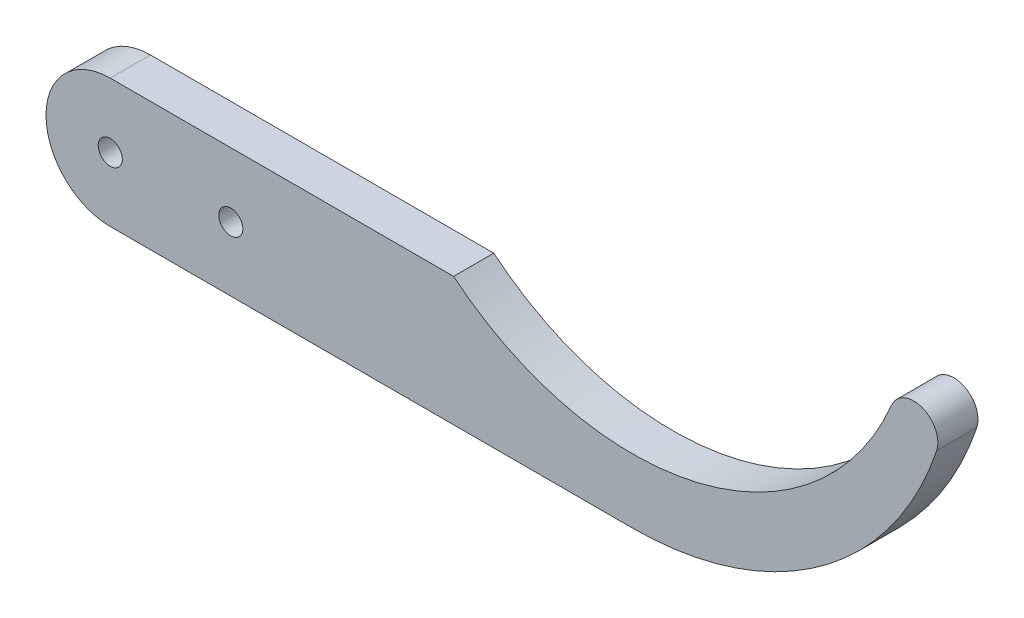
SolidWorks part; units mm, degrees
ref_plane "Plan de face" through (0, 0, 0) normal (0, 0, 1) x (1, 0, 0)
ref_plane "Plan de dessus" through (0, 0, 0) normal (0, 1, 0) x (1, 0, 0)
ref_plane "Plan de droite" through (0, 0, 0) normal (1, 0, 0) x (0, 0, -1)
sketch "Esquisse1" plane through (0, 0, 0) normal (0, 0, 1) x (1, 0, 0)
  line L0 (0, 0) -> (80, 0) construction
  line L1 (20, 0) -> (20, 23.8674) construction
  line L2 (0, 0) -> (0, 35) construction
  line L3 (0, 35) -> (50, 35) construction
  line L4 (0, 8) -> (20, 8)
  line L5 (82.2368, 21.3697) -> (85, 20.2014) construction
  line L6 (20, 8) -> (27.7289, 8)
  line L7 (0, -8) -> (50, -8)
  line L8 (50, 35) -> (50, -8) construction
  line L9 (0, 8) -> (-15, 8)
  line L10 (0, 0) -> (-15, 0) construction
  line L11 (0, -8) -> (-15, -8)
  circle A0 centre (0, 0) radius 1.5
  arc A1 (0, 8) -> (0, -8) centre (0, 0) ccw construction
  circle A2 centre (50, 35) radius 35 construction
  arc A3 (27.7289, 8) -> (82.2368, 21.3697) centre (50, 35) ccw
  arc A4 (82.2368, 21.3697) -> (87.8451, 19.25) centre (85, 20.2014) cw
  arc A5 (50, -8) -> (87.8451, 19.25) centre (50, 31.9049) ccw
  circle A6 centre (15, 0) radius 1.5 construction
  arc A7 (-15, 8) -> (-15, -8) centre (-15, 0) ccw
  circle A8 centre (-15, 0) radius 1.5
  dimension "D3" = 3
  dimension "D4" = 35
  dimension "D6" = 70
  dimension "D7" = 3
  dimension "D8" = 8
  dimension "D9" = 35
  dimension "D10" = 15
  dimension "D11" = 8
  dimension "D1" = 20
  dimension "D2" = 80
  dimension "D5" = 50
  dimension "D12" = 15
extrude "Boss.-Extru.1" add sketch "Esquisse1" along normal blind 5
